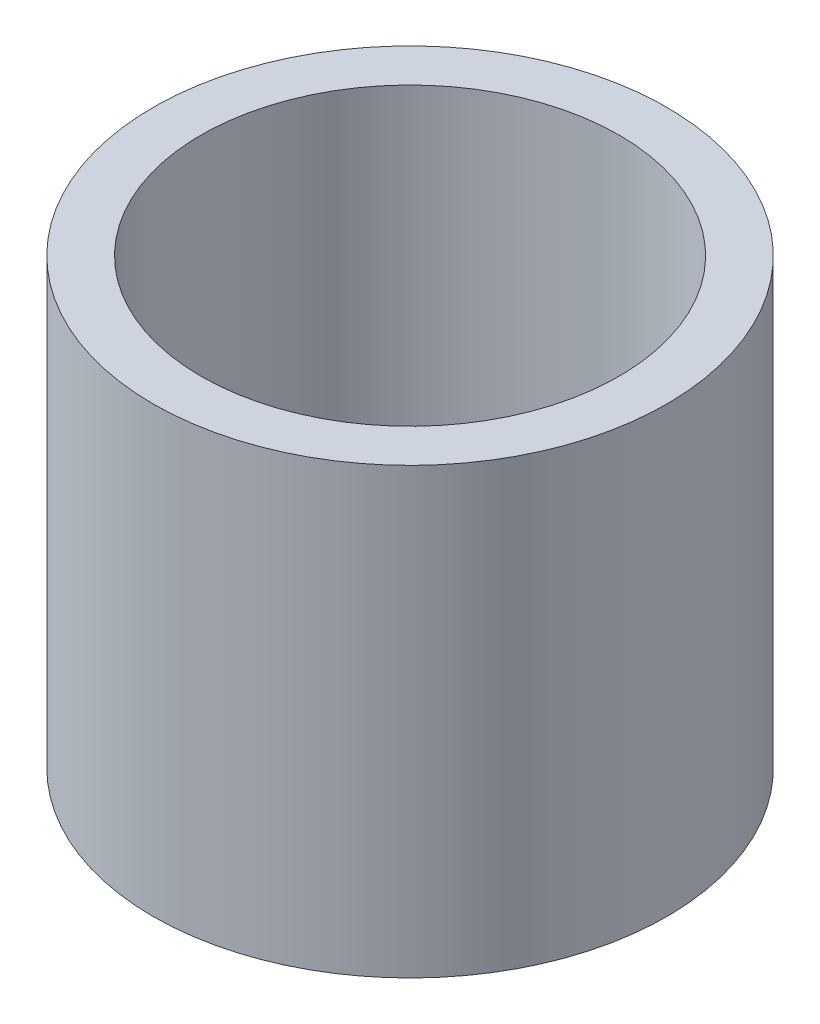
SolidWorks part; units mm, degrees
ref_plane "Front Plane" through (0, 0, 0) normal (0, 0, 1) x (1, 0, 0)
ref_plane "Top Plane" through (0, 0, 0) normal (0, 1, 0) x (1, 0, 0)
ref_plane "Right Plane" through (0, 0, 0) normal (1, 0, 0) x (0, 0, -1)
sketch "Sketch1" plane through (0, 0, 0) normal (0, 1, 0) x (1, 0, 0)
  circle A0 centre (0, 0) radius 20
  dimension "SLEEVE_OD" = 40
extrude "Boss-Extrude1" add sketch "Sketch1" along normal blind 34.5652
sketch "Sketch2" plane through (0, 0, 0) normal (0, 1, 0) x (1, 0, 0)
  circle A0 centre (0, 0) radius 16.2732
  dimension "BORE_D" = 32.5464
extrude "Cut-Extrude1" cut sketch "Sketch2" along normal through all
chamfer "Chamfer1" distance 3.1072 angle 60 rebuild error yes
